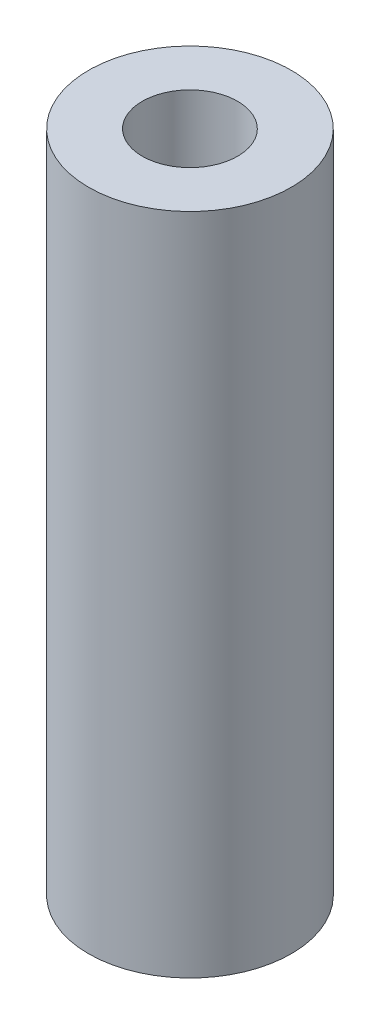
SolidWorks part; units mm, degrees
ref_plane "Front Plane" through (0, 0, 0) normal (0, 0, 1) x (1, 0, 0)
ref_plane "Top Plane" through (0, 0, 0) normal (0, 1, 0) x (1, 0, 0)
ref_plane "Right Plane" through (0, 0, 0) normal (1, 0, 0) x (0, 0, -1)
sketch "Sketch1" plane through (0, 0, 0) normal (0, 1, 0) x (1, 0, 0)
  circle A0 centre (0, 0) radius 5.955
  dimension "D1" = 11.91
extrude "Boss-Extrude1" add sketch "Sketch1" along normal blind 39
sketch "Sketch2" plane through (0, 39, 0) normal (0, 1, 0) x (1, 0, 0)
  circle A0 centre (0, 0) radius 2.8
  dimension "D1" = 5.6
extrude "Cut-Extrude1" cut sketch "Sketch2" against normal blind 4.5
sketch "Sketch3" plane through (0, 0, 0) normal (0, -1, 0) x (1, 0, 0)
  circle A0 centre (0, 0) radius 9.645
extrude "Cut-Extrude2" [suppressed] cut sketch "Sketch3" against normal blind 33
sketch "Sketch4" plane through (0, 39, 0) normal (0, 1, 0) x (1, 0, 0)
  circle A0 centre (0, 0) radius 5.955
  circle A1 centre (0, 0) radius 3.5804
extrude "Cut-Extrude3" [suppressed] cut sketch "Sketch4" against normal blind 30
